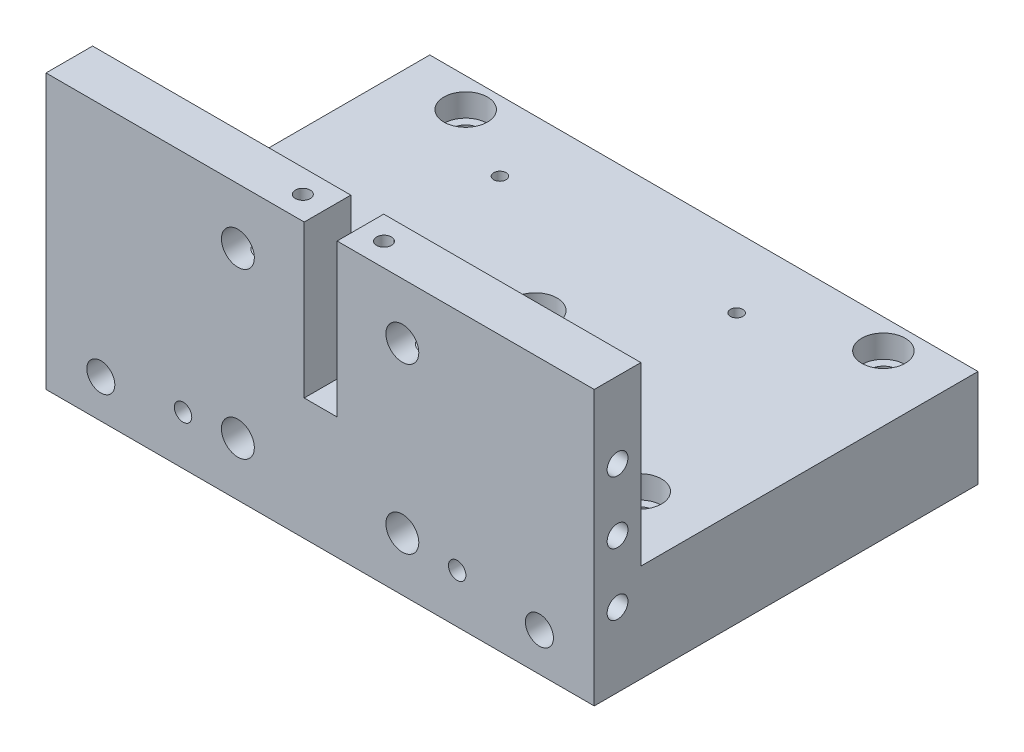
SolidWorks part; units mm, degrees
note: '?' marks a value the reader was unsure of.
ref_plane "Front" through (0, 0, 0) normal (0, 0, 1) x (1, 0, 0)
ref_plane "Top" through (0, 0, 0) normal (0, 1, 0) x (1, 0, 0)
ref_plane "Right" through (0, 0, 0) normal (1, 0, 0) x (0, 0, -1)
sketch "Sketch1" plane through (0, 0, 0) normal (0, 0, 1) x (1, 0, 0)
  line L1 (0, 0) -> (100, 0)
  line L2 (0, 0) -> (0, 50)
  line L3 (0, 50) -> (100, 50)
  line L4 (100, 0) -> (100, 50)
  dimension "D1" = 100
  dimension "D2" = 50
extrude "Boss-Extrude1" add sketch "Sketch1" along normal blind 70
sketch "Laser center" plane through (0, 0, 70) normal (0, 0, 1) x (1, 0, 0)
  line L0 (0, 0) -> (100, 0) construction
  line L1 (50, 24.8) -> (50, 0) construction
  point P0 (50, 24.8)
  dimension "D1" = 24.8
ref_axis "Optical axis" through (50, 24.8, 70) along (0, 0, 1)?
sketch "Sketch3" plane through (0, 0, 70) normal (0, 0, 1) x (1, 0, 0)
  line L0 (50, 50) -> (50, 22.2)
  line L1 (50, 50) -> (47.1, 50)
  line L2 (50, 22.2) -> (47.1, 22.2)
  line L3 (47.1, 50) -> (47.1, 22.2)
  line L4 (100, 50) -> (0, 50) construction
  line L5 (0, 0) -> (100, 0) construction
  dimension "D1" = 2.9
  dimension "D2" = 22.2
extrude "Cut-Extrude - 2.9 width" cut sketch "Sketch3" against normal through all
sketch "Sketch4" plane through (0, 0, 70) normal (0, 0, 1) x (1, 0, 0)
  line L0 (50, 50) -> (50, 22.2)
  line L1 (50, 50) -> (53.1, 50)
  line L2 (50, 22.2) -> (53.1, 22.2)
  line L3 (53.1, 50) -> (53.1, 22.2)
  dimension "D1" = 3.1
extrude "Cut-Extrude - 3.1 width" cut sketch "Sketch4" against normal through all
sketch "Sketch5" plane through (100, 0, 0) normal (1, 0, 0) x (0, 0, -1)
  line L0 (-61.5, 50) -> (-61.5, 17.8404)
  line L1 (-61.5, 50) -> (0, 50)
  line L2 (-61.5, 17.8404) -> (0, 17.8404)
  line L3 (0, 50) -> (0, 17.8404)
  line L4 (-70, 50) -> (0, 50) construction
  line L5 (-70, 0) -> (-70, 50) construction
  line L7 (0, 0) -> (0, 50) construction
  line L9 (0, 22.2) -> (-70, 22.2) construction
  dimension "D1" = 8.5
  dimension "D2" = 4.3596
  dimension "D3" = 0
extrude "Cut-Extrude4" cut sketch "Sketch5" against normal through all
hole_wizard "#6-32 Tapped Hole - laser lateral pressure" positions "Sketch7" profile "Sketch6" tap size "#6-32" standard "ANSI Inch"
sketch "Sketch7" plane through (100, 0, 0) normal (1, 0, 0) x (0, 0, -1)
  line L0 (-70, 0) -> (0, 0) construction
  line L1 (-70, 0) -> (-70, 50) construction
  point P0 (-65.75, 24.8)
  dimension "D1" = 24.8
  dimension "D2" = 4.25
sketch "Sketch6" plane through (100, 24.8, 65.75) normal (0, 1, 0) x (0, 0, -1)
  line L0 (0, 0) -> (0, 47.7117)
  line L1 (0, 47.7117) -> (1.3525, 46.899)
  line L2 (1.3525, 46.899) -> (1.3525, 0)
  line L5 (1.3525, 0) -> (0, 0)
  line L10 (0, 47.7117) -> (-1.3526, 46.899) construction
  line L11 (0, -6.35) -> (0, 107.95) construction
  dimension "Tap Drill Dia." = 2.7051
  dimension "Tap Drill Depth" = 46.899
  dimension "Drill Angle" = 118
cosmetic thread "Hole Thread1" parameters "D1"=12.7, "D2"=3.5052
hole_wizard "#25 (0.1495) Diameter Hole3" positions "Sketch47" profile "Sketch46" hole size "#25" standard "ANSI Inch"
sketch "Sketch47" plane through (100, 0, 0) normal (1, 0, 0) x (0, 0, -1)
  point P0 (-65.75, 24.8)
sketch "Sketch46" plane through (100, 24.8, 65.75) normal (0, 1, 0) x (0, 0, -1)
  line L0 (0, 0) -> (0, 35.1408)
  line L1 (0, 35.1408) -> (1.8986, 34)
  line L2 (1.8986, 34) -> (1.8986, 0)
  line L5 (1.8986, 0) -> (0, 0)
  line L10 (0, 35.1408) -> (-1.8987, 34) construction
  line L11 (0, -6.35) -> (0, 107.95) construction
  dimension "Hole Dia." = 3.7973
  dimension "Hole Depth" = 34
  dimension "Drill Angle" = 118
ref_plane "Optical axis normal plane" through (50, 0, 0) normal (1, 0, 0) x (0, 0, -1)
sketch "Sketch10" plane through (0, 0, 70) normal (0, 0, 1) x (1, 0, 0)
  circle A0 centre (35, 39.8) radius 3
  dimension "D3" = 15
  dimension "D4" = 15
extrude "Cut-Extrude - ER rods" cut sketch "Sketch10" against normal up to surface (8.5 mm away) up to face at (50.05, 35.0101, 61.5)
pattern_linear "LPattern3" count 2 spacing 30 along (0, -1, 0) count 2 spacing 30 along (1, 0, 0) of "Cut-Extrude - ER rods"
ref_plane "Plane3" through (38, 0, 0) normal (-1, 0, 0) x (0, 0, 1)
ref_plane "Plane4" through (0, 39.8, 0) normal (0, 1, 0) x (1, 0, 0)
ref_plane "Plane7" through (62, 0, 0) normal (1, 0, 0) x (0, 0, -1)
hole_wizard "#4-40 Tapped Hole6" positions "3DSketch1" profile "Sketch28" tap size "#4-40" standard "ANSI Inch"
sketch3d "3DSketch1"
  line L4 (0, 50, 70) -> (0, 0, 70) construction
  line L5 (0, 50, 61.5) -> (0, 17.8404, 61.5) construction
  line L6 (0, 36.2145, 70) -> (0, 36.0455, 61.5) construction
  point P0 (0, 36.13, 65.75)
  dimension "D1" = 3.67
sketch "Sketch28" plane through (0, 36.13, 65.75) normal (0, 1, 0) x (0, 0, 1)
  line L0 (0, 0) -> (0, 38.6782)
  line L1 (0, 38.6782) -> (1.1303, 37.999)
  line L2 (1.1303, 37.999) -> (1.1303, 0)
  line L5 (1.1303, 0) -> (0, 0)
  line L10 (0, 38.6782) -> (-1.1303, 37.999) construction
  line L11 (0, -6.35) -> (0, 107.95) construction
  dimension "Tap Drill Dia." = 2.2606
  dimension "Tap Drill Depth" = 37.999
  dimension "Drill Angle" = 118
cosmetic thread "Hole Thread6" parameters "D1"=5.69, "D2"=2.8448
hole_wizard "#4-40 Tapped Hole7" positions "3DSketch2" profile "Sketch29" tap size "#4-40" standard "ANSI Inch"
sketch3d "3DSketch2"
  line L0 (38, 36.13, 65.75) -> (0, 36.13, 65.75) construction
  line L1 (100, 36.13, 70) -> (100, 36.13, 61.5) construction
  line L2 (100, 0, 70) -> (100, 50, 70) construction
  line L3 (100, 50, 61.5) -> (100, 17.8404, 61.5) construction
  point P0 (100, 36.13, 65.75)
sketch "Sketch29" plane through (100, 36.13, 65.75) normal (0, 1, 0) x (0, 0, -1)
  line L0 (0, 0) -> (0, 38.6782)
  line L1 (0, 38.6782) -> (1.1303, 37.999)
  line L2 (1.1303, 37.999) -> (1.1303, 0)
  line L5 (1.1303, 0) -> (0, 0)
  line L10 (0, 38.6782) -> (-1.1303, 37.999) construction
  line L11 (0, -6.35) -> (0, 107.95) construction
  dimension "Tap Drill Dia." = 2.2606
  dimension "Tap Drill Depth" = 37.999
  dimension "Drill Angle" = 118
cosmetic thread "Hole Thread7" parameters "D1"=5.69, "D2"=2.8448
hole_wizard "#25 (0.1495) Diameter Hole1" positions "Sketch43" profile "Sketch42" hole size "#25" standard "ANSI Inch"
sketch "Sketch43" plane through (0, 0, 0) normal (-1, 0, 0) x (0, 0, 1)
  point P0 (65.75, 36.13)
sketch "Sketch42" plane through (0, 36.13, 65.75) normal (0, 1, 0) x (0, 0, 1)
  line L0 (0, 0) -> (0, 30.1408)
  line L1 (0, 30.1408) -> (1.8986, 29)
  line L2 (1.8986, 29) -> (1.8986, 0)
  line L5 (1.8986, 0) -> (0, 0)
  line L10 (0, 30.1408) -> (-1.8987, 29) construction
  line L11 (0, -6.35) -> (0, 107.95) construction
  dimension "Hole Dia." = 3.7973
  dimension "Hole Depth" = 29
  dimension "Drill Angle" = 118
hole_wizard "#25 (0.1495) Diameter Hole2" positions "Sketch45" profile "Sketch44" hole size "#25" standard "ANSI Inch"
sketch "Sketch45" plane through (100, 0, 0) normal (1, 0, 0) x (0, 0, -1)
  point P2 (-65.75, 36.13)
sketch "Sketch44" plane through (100, 36.13, 65.75) normal (0, 1, 0) x (0, 0, -1)
  line L0 (0, 0) -> (0, 30.1408)
  line L1 (0, 30.1408) -> (1.8986, 29)
  line L2 (1.8986, 29) -> (1.8986, 0)
  line L5 (1.8986, 0) -> (0, 0)
  line L10 (0, 30.1408) -> (-1.8986, 29) construction
  line L11 (0, -6.35) -> (0, 107.95) construction
  dimension "Hole Dia." = 3.7973
  dimension "Hole Depth" = 29
  dimension "Drill Angle" = 118
ref_plane "Plane5" through (0, 24.8, 0) normal (0, 1, 0) x (1, 0, 0)
mirror "Mirror3" about plane through (0, 24.8, 0) normal (0, 1, 0) of "#25 (0.1495) Diameter Hole2", "#25 (0.1495) Diameter Hole1", "#4-40 Tapped Hole6", "#4-40 Tapped Hole7"
hole_wizard "#6-32 Tapped Hole - laser vertical pressure" positions "Sketch23" profile "Sketch22" tap size "#6-32" standard "ANSI Inch"
sketch "Sketch23" plane through (0, 50, 0) normal (0, 1, 0) x (1, 0, 0)
  line L0 (47.1, -70) -> (0, -70) construction
  line L1 (47.1, -61.5) -> (47.1, -70) construction
  point P0 (42.6, -65.75)
  dimension "D1" = 4.25
  dimension "D2" = 4.5
sketch "Sketch22" plane through (42.6, 50, 65.75) normal (1, 0, 0) x (0, 0, 1)
  line L0 (0, 0) -> (0, 11.7827)
  line L1 (0, 11.7827) -> (1.3525, 10.97)
  line L2 (1.3525, 10.97) -> (1.3525, 0)
  line L5 (1.3525, 0) -> (0, 0)
  line L10 (0, 11.7827) -> (-1.3526, 10.97) construction
  line L11 (0, -6.35) -> (0, 107.95) construction
  dimension "Tap Drill Dia." = 2.7051
  dimension "Tap Drill Depth" = 10.97
  dimension "Drill Angle" = 118
cosmetic thread "Hole Thread3" parameters "D1"=7.01, "D2"=3.5052
mirror "Mirror1" about plane through (50, 0, 0) normal (1, 0, 0) of "#6-32 Tapped Hole - laser vertical pressure"
ref_plane "Mid-LD pins" through (50.9525, 0, 0) normal (1, 0, 0) x (0, 0, -1)
hole_wizard "#4-40 Tapped Hole - pulse board" positions "Sketch25" profile "Sketch24" tap size "#4-40" standard "ANSI Inch"
sketch "Sketch25" plane through (0, 17.8404, 0) normal (0, 1, 0) x (1, 0, 0)
  line L0 (0, -61.5) -> (100, -61.5) construction
  line L1 (50.9525, -4.675) -> (50.9525, 4.675) construction
  point P0 (68.7325, -55.936)
  dimension "D1" = 5.564
  dimension "D2" = 17.78
sketch "Sketch24" plane through (68.7325, 17.8404, 55.936) normal (1, 0, 0) x (0, 0, 1)
  line L0 (0, 0) -> (0, 4.6792)
  line L1 (0, 4.6792) -> (1.1303, 4)
  line L2 (1.1303, 4) -> (1.1303, 0)
  line L5 (1.1303, 0) -> (0, 0)
  line L10 (0, 4.6792) -> (-1.1303, 4) construction
  line L11 (0, -6.35) -> (0, 107.95) construction
  dimension "Tap Drill Dia." = 2.2606
  dimension "Tap Drill Depth" = 4
  dimension "Drill Angle" = 118
cosmetic thread "Hole Thread4" parameters "D1"=4, "D2"=2.8448
pattern_linear "Pulse board mounting holes" count 2 spacing 43.18 along (0, 0, -1) count 2 spacing 43.18 along (-1, 0, 0) of "#4-40 Tapped Hole - pulse board"
hole_wizard "#2-56 Tapped Hole - pulse board heat transfer block" positions "Sketch27" profile "Sketch26" tap size "#2-56" standard "ANSI Inch"
sketch "Sketch27" plane through (0, 17.8404, 0) normal (0, 1, 0) x (1, 0, 0)
  point P0 (26.1875, -34.346)
  dimension "D1" = 21.59
  dimension "D2" = 0.635
sketch "Sketch26" plane through (26.1875, 17.8404, 34.346) normal (1, 0, 0) x (0, 0, 1)
  line L0 (0, 0) -> (0, 7.1742)
  line L1 (0, 7.1742) -> (0.889, 6.64)
  line L2 (0.889, 6.64) -> (0.889, 0)
  line L5 (0.889, 0) -> (0, 0)
  line L10 (0, 7.1742) -> (-0.889, 6.64) construction
  line L11 (0, -6.35) -> (0, 107.95) construction
  dimension "Tap Drill Dia." = 1.778
  dimension "Tap Drill Depth" = 6.64
  dimension "Drill Angle" = 118
cosmetic thread "Hole Thread5" parameters "D1"=4.37, "D2"=2.1844
ref_plane "Plane8" through (0, 17.8404, 0) normal (0, 1, 0) x (1, 0, 0)
sketch "Sketch37" plane through (0, 0, 70) normal (0, 0, 1) x (1, 0, 0)
  line L0 (0, 9.8) -> (35, 9.8) construction
  line L1 (0, 50) -> (0, 0) construction
  line L2 (25, 0) -> (25, 17.8404) construction
  line L3 (0, 0) -> (100, 0) construction
  line L4 (33.825, 17.8404) -> (-33.825, 17.8404) construction
  line L5 (50, 24.8) -> (50, 0) construction
  circle A0 centre (25, 8.9202) radius 1.5875
  dimension "D1" = 25
  dimension "D2" = 3.175
extrude "1/8 x 3/4 Dowel slot" cut sketch "Sketch37" against normal blind 17
hole_wizard "0.2\" hole for #10 connection screw" positions "Sketch35" profile "Sketch34" hole size "#10" standard "ANSI Inch"
sketch "Sketch35" plane through (0, 0, 70) normal (0, 0, 1) x (1, 0, 0)
  line L1 (0, 0) -> (100, 0) construction
  line L2 (0, 50) -> (0, 0) construction
  point P5 (10, 7)
  dimension "D1" = 7
  dimension "D2" = 10
sketch "Sketch34" plane through (10, 7, 70) normal (1, 0, 0) x (0, -1, 0)
  line L0 (0, 0) -> (0, 18.5338)
  line L1 (0, 18.5338) -> (2.5527, 17)
  line L2 (2.5527, 17) -> (2.5527, 0)
  line L5 (2.5527, 0) -> (0, 0)
  line L10 (0, 18.5338) -> (-2.5527, 17) construction
  line L11 (0, -6.35) -> (0, 107.95) construction
  dimension "Hole Dia." = 5.1054
  dimension "Hole Depth" = 17
  dimension "Drill Angle" = 118
mirror "Mirror6" about plane through (50, 0, 0) normal (1, 0, 0) of "0.2\" hole for #10 connection screw", "1/8 x 3/4 Dowel slot"
hole_wizard "CBORE for #8 Socket Head Cap Screw1" positions "Sketch41" profile "Sketch38" counterbore size "#8" standard "ANSI Inch" end condition through all
sketch "Sketch41" plane through (0, 17.8404, 0) normal (0, 1, 0) x (1, 0, 0)
  line L1 (0, 0) -> (100, 0) construction
  line L4 (50, -5.35) -> (88.1, -5.35) construction
  line L5 (88.1, -5.35) -> (88.1, -49.8) construction
  point P0 (50, -30.75)
  point P2 (88.1, -5.35)
  point P4 (88.1, -49.8)
  dimension "D1" = 38.1
  dimension "D2" = 44.45
  dimension "D3" = 5.35
sketch "Sketch38" plane through (50, 17.8404, 30.75) normal (1, 0, 0) x (0, 0, 1)
  line L0 (0, 0) -> (0, 17.8404)
  line L1 (0, 17.8404) -> (2.4574, 17.8404)
  line L3 (2.4574, 17.8404) -> (2.4574, 4.1656)
  line L4 (2.4574, 4.1656) -> (3.9687, 4.1656)
  line L5 (3.9687, 4.1656) -> (3.9687, 0)
  line L7 (3.9687, 0) -> (0, 0)
  line L11 (0, -6.35) -> (0, 107.95) construction
  dimension "Thru Hole Dia." = 4.9149
  dimension "Thru Hole Depth" = 17.8404
  dimension "C'Bore Dia." = 7.9375
  dimension "C'Bore Depth" = 4.1656
mirror "Mirror7" about plane through (50, 0, 0) normal (1, 0, 0) of "CBORE for #8 Socket Head Cap Screw1"
